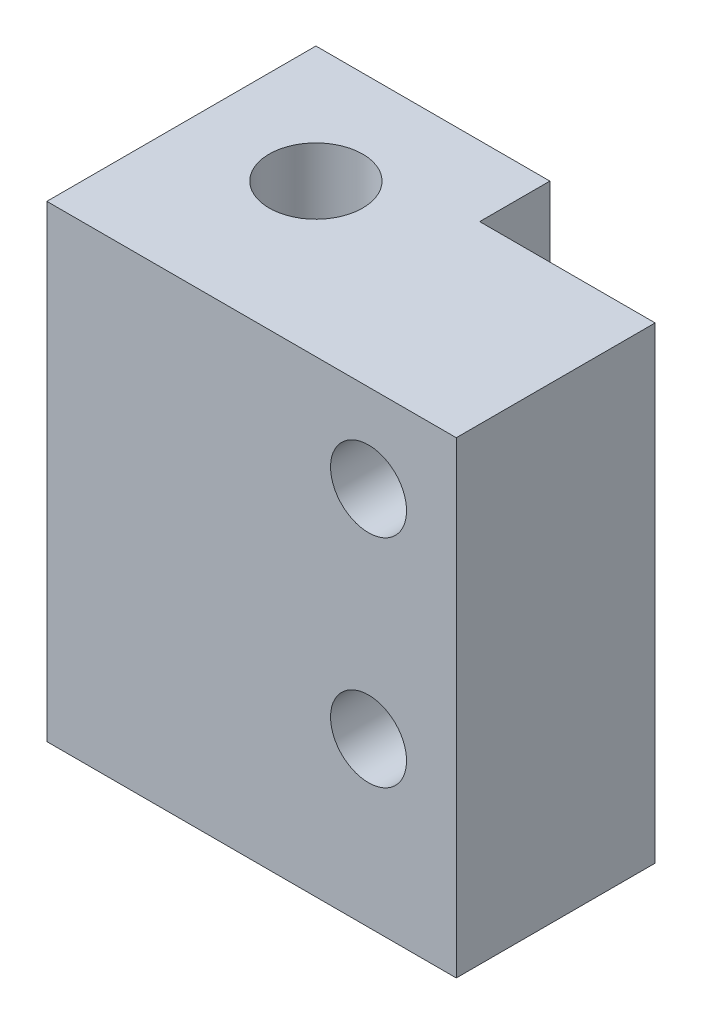
SolidWorks part; units mm, degrees
ref_plane "Front Plane" through (0, 0, 0) normal (0, 0, 1) x (1, 0, 0)
ref_plane "Top Plane" through (0, 0, 0) normal (0, 1, 0) x (1, 0, 0)
ref_plane "Right Plane" through (0, 0, 0) normal (1, 0, 0) x (0, 0, -1)
sketch "Sketch1" plane through (0, 0, 0) normal (0, 1, 0) x (1, 0, 0)
  line L5 (-10, -5.2575) -> (-10, 0.7425)
  line L6 (-10, 0.7425) -> (10, 0.7425)
  line L9 (25, -5.2575) -> (25, -22.2575)
  line L10 (0, -22.2575) -> (0, 0.7425) construction
  line L11 (-10, -5.2575) -> (-10, -22.2575)
  line L12 (10, 0.7425) -> (10, -5.2575)
  line L13 (10, -5.2575) -> (25, -5.2575)
  line L14 (-10, -22.2575) -> (25, -22.2575)
  point P2 (0, 0)
  dimension "D5" = 17
  dimension "D6" = 15
extrude "Boss-Extrude2" add sketch "Sketch1" along normal blind 40
sketch "Sketch3" plane through (0, 0, 0) normal (0, -1, 0) x (1, 0, 0)
  line L0 (0, -0.7425) -> (0, 22.2575) construction
  line L1 (10, -0.7425) -> (-10, -0.7425) construction
  circle A0 centre (0, 9.2575) radius 4
  dimension "D1" = 8
  dimension "D2" = 10
extrude "Cut-Extrude1" cut sketch "Sketch3" against normal blind 35
sketch "Sketch4" plane through (0, 0, 5.2575) normal (0, 0, -1) x (-1, 0, 0)
  line L0 (-25, 20) -> (-10, 20) construction
  line L1 (-25, 40) -> (-25, 0) construction
  line L2 (-10, 40) -> (-10, 0) construction
  line L3 (-17.5, 40) -> (-17.5, 0) construction
  line L4 (-25, 40) -> (-10, 40) construction
  line L5 (-25, 0) -> (-10, 0) construction
  circle A0 centre (-17.5, 26.0458) radius 3.25
  circle A2 centre (-17.5, 7.5353) radius 3.25
  dimension "D1" = 6.5
  dimension "D2" = 6.5
extrude "Cut-Extrude2" cut sketch "Sketch4" against normal up to next
sketch "Sketch5" plane through (0, 0, 0) normal (0, -1, 0) x (1, 0, 0)
  line L0 (0, -0.7425) -> (0, 22.2575) construction
  line L1 (10, -0.7425) -> (-10, -0.7425) construction
  line L2 (-10, 22.2575) -> (25, 22.2575) construction
mirror "Mirror4" about plane through (0, 0, 0) normal (0, 1, 0) of bodies 104
delete or keep bodies "Body-Delete/Keep 1" type keep bodies bodies 108
